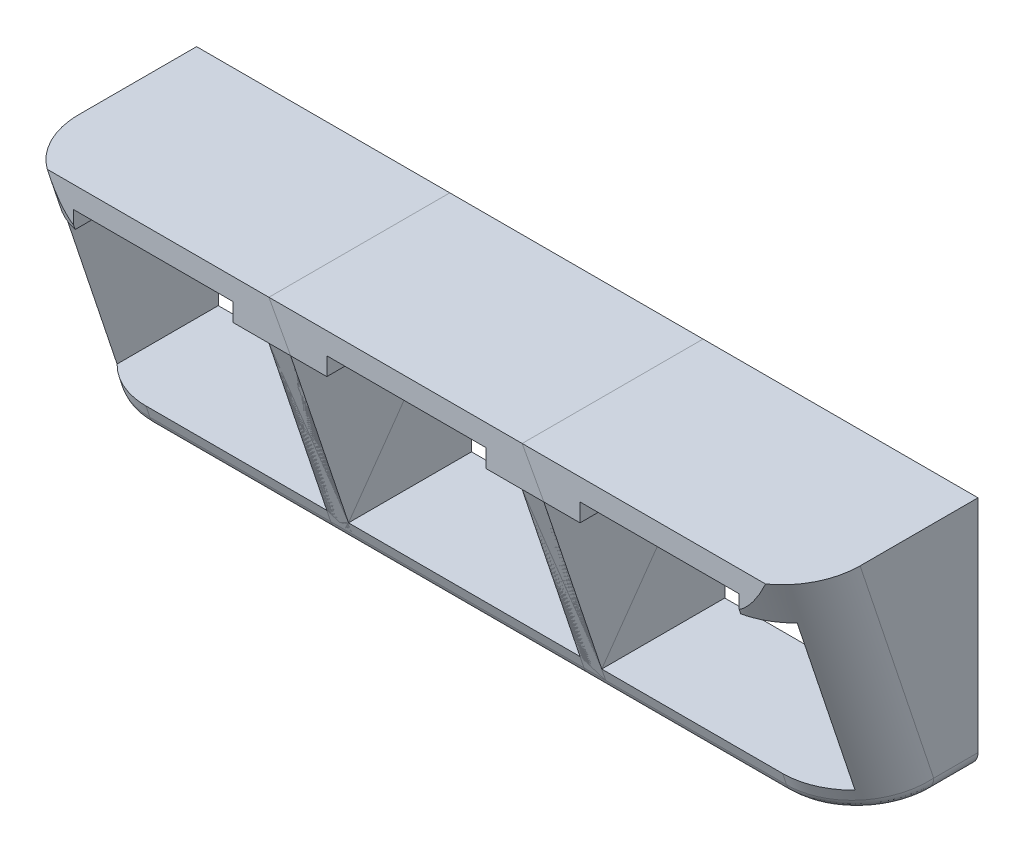
SolidWorks part; units mm, degrees
ref_plane "Front Plane" through (0, 0, 0) normal (0, 0, 1) x (1, 0, 0)
ref_plane "Top Plane" through (0, 0, 0) normal (0, 1, 0) x (1, 0, 0)
ref_plane "Right Plane" through (0, 0, 0) normal (1, 0, 0) x (0, 0, -1)
sketch "Sketch1" plane through (0, 0, 0) normal (0, 0, 1) x (1, 0, 0)
  line L0 (8, 27) -> (8, 29.5)
  line L1 (3, 3) -> (35, 3)
  line L2 (3, 3) -> (3, 27)
  line L3 (3, 27) -> (8, 27)
  line L4 (35, 3) -> (35, 27)
  line L5 (8, 29.5) -> (30, 29.5)
  line L6 (30, 29.5) -> (30, 27)
  line L7 (30, 27) -> (35, 27)
  line L9 (0, 0) -> (38, 0)
  line L10 (0, 0) -> (0, 32.5)
  line L11 (0, 32.5) -> (38, 32.5)
  line L12 (38, 0) -> (38, 32.5)
  point P4 (19, 29.5)
  point P10 (19, 3)
  dimension "D1" = 24
  dimension "D2" = 32
  dimension "D3" = 26.5
  dimension "D4" = 22
  dimension "D5" = 3
  dimension "D6" = 3
  dimension "D7" = 3
  dimension "D8" = 3
extrude "Boss-Extrude1" add sketch "Sketch1" along normal blind 25
sketch "Sketch3" plane through (0, 29.5, 0) normal (0, -1, 0) x (1, 0, 0)
  line L1 (8, 0) -> (30, 0)
  line L2 (8, 0) -> (8, 11)
  line L3 (8, 11) -> (16, 11)
  line L4 (30, 0) -> (30, 11)
  line L5 (30, 25) -> (30, 0) construction
  line L7 (16, 11) -> (16, 9.5)
  line L8 (16, 9.5) -> (22, 9.5)
  line L9 (22, 9.5) -> (22, 11)
  line L10 (22, 11) -> (30, 11)
  point P4 (19, 9.5)
  point P12 (19, 0)
  dimension "D1" = 11
  dimension "D2" = 6
  dimension "D3" = 1.5
extrude "Boss-Extrude2" add sketch "Sketch3" along normal up to surface (2.5 mm away) up to face at (5.5, 27, 12.5)
sketch "Sketch4" plane through (0, 0, 0) normal (-1, 0, 0) x (0, 0, 1)
  line L0 (25, 27) -> (16, 0)
  line L1 (25, 32.5) -> (25, 0) construction
  line L2 (25, 0) -> (0, 0) construction
  line L3 (16, 0) -> (25, 0)
  line L4 (25, 0) -> (25, 27)
  line L5 (0, 32.5) -> (0, 0) construction
  point P10 (25, 0)
  point P11 (25, 19.4566)
  dimension "D1" = 16
extrude "Cut-Extrude1" cut sketch "Sketch4" against normal up to surface (38 mm away) up to face at (38, 16.25, 12.5)
sketch "Sketch6" plane through (22, 0, 0) normal (-1, 0, 0) x (0, 0, 1)
  line L0 (11, 29.5) -> (9.5, 29.5) construction
  line L1 (9.5, 29.5) -> (11.14, 27.86)
  line L2 (11.14, 27.86) -> (15.5, 29.5)
  line L3 (15.5, 29.5) -> (9.5, 29.5)
  line L4 (25, 29.5) -> (11, 29.5) construction
  line L5 (11, 27) -> (11, 29.5) construction
  point P1 (9.7941, 29.5)
  point P7 (13.3509, 29.5)
  point P10 (11, 28)
  point P14 (11, 28)
  dimension "D1" = 1
  dimension "D2" = 6
  dimension "D3" = 0.14
extrude "Boss-Extrude3" add sketch "Sketch6" along normal offset from surface (3 mm away) 1.5 from offset 1.5 up to face at (16, 28.25, 10.25)
pattern_linear "LPattern1" count 3 spacing 35 along (1, 0, 0) of bodies 104
fillet "Fillet1" radius 10 1 edges at (108, 13.5, 20.5)
fillet "Fillet2" radius 10 1 edges at (0, 13.5, 20.5)
fillet "Fillet3" radius 2 3 edges at (0, 0, 2.7295) (2.9289, 0, 12.9126) (24, 0, 16)
fillet "Fillet4" radius 2 1 edges at (54, 0, 16)
fillet "Fillet5" radius 2 3 edges at (108, 0, 2.7295) (105.0711, 0, 12.9126) (84, 0, 16)
